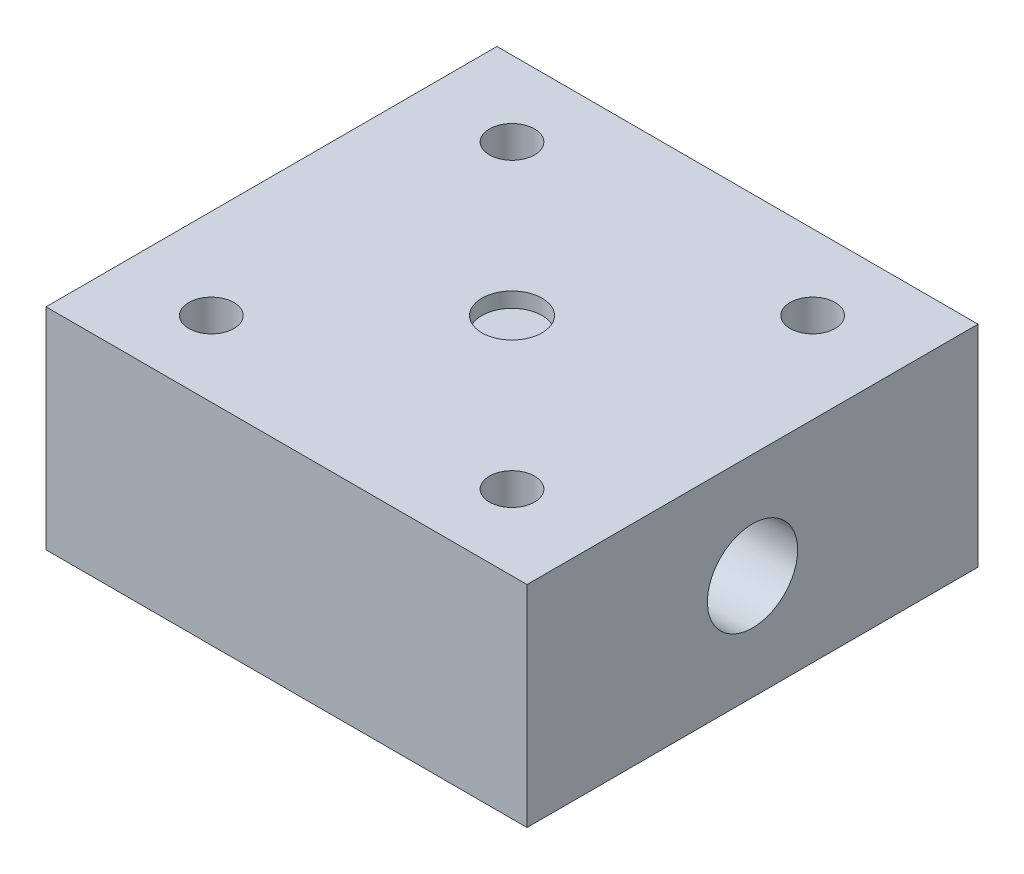
SolidWorks part; units mm, degrees
material "普通碳钢"
ref_plane "前视基准面" through (0, 0, 0) normal (0, 0, 1) x (1, 0, 0)
ref_plane "上视基准面" through (0, 0, 0) normal (0, 1, 0) x (1, 0, 0)
ref_plane "右视基准面" through (0, 0, 0) normal (1, 0, 0) x (0, 0, -1)
sketch "草图1" plane through (0, 0, 0) normal (0, 0, 1) x (1, 0, 0)
  line L1 (-16, -7) -> (16, -7)
  line L2 (-16, -7) -> (-16, 7)
  line L3 (-16, 7) -> (16, 7)
  line L4 (16, -7) -> (16, 7)
  line L5 (-16, -7) -> (16, 7) construction
  line L6 (-16, 7) -> (16, -7) construction
  point P0 (0, 0)
  dimension "D1" = 32
  dimension "D2" = 14
extrude "凸台-拉伸1" add sketch "草图1" against normal blind 30
sketch "草图2" plane through (0, 7, 0) normal (0, 1, 0) x (1, 0, 0)
  line L0 (0, 30) -> (0, 0) construction
  line L1 (16, 30) -> (-16, 30) construction
  line L2 (16, 0) -> (-16, 0) construction
  line L3 (-16, 15) -> (16, 15) construction
  line L4 (-16, 30) -> (-16, 0) construction
  line L5 (16, 30) -> (16, 0) construction
  circle A0 centre (-10, 25) radius 1.5
  circle A1 centre (10, 25) radius 1.5
  circle A2 centre (10, 5) radius 1.5
  circle A3 centre (-10, 5) radius 1.5
  dimension "D1" = 3
  dimension "D2" = 10
  dimension "D3" = 10
extrude "切除-拉伸1" cut sketch "草图2" against normal blind 10
sketch "草图3" plane through (16, 0, 0) normal (1, 0, 0) x (0, 0, -1)
  line L0 (15, 7) -> (15, -7) construction
  line L1 (30, 7) -> (0, 7) construction
  line L2 (30, -7) -> (0, -7) construction
  circle A0 centre (15, 0) radius 3
  dimension "D1" = 6
extrude "切除-拉伸2" cut sketch "草图3" against normal up to next
sketch "Sketch1" plane through (0, 7, 0) normal (0, 1, 0) x (1, 0, 0)
  line L0 (0, 0) -> (0, 30) construction
  line L1 (16, 30) -> (-16, 30) construction
  circle A0 centre (0, 15) radius 2
  dimension "D1" = 4
extrude "Cut-Extrude1" cut sketch "Sketch1" against normal blind 1
